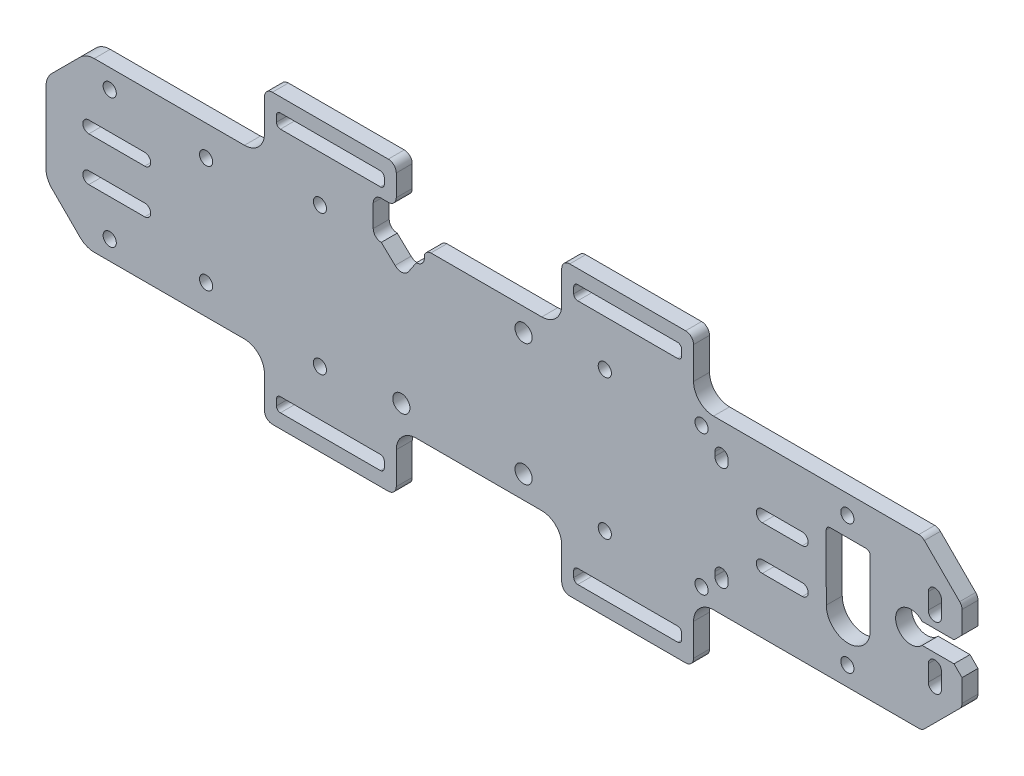
SolidWorks part; units mm, degrees
ref_plane "Спереди" through (0, 0, 0) normal (0, 0, 1) x (1, 0, 0)
ref_plane "Сверху" through (0, 0, 0) normal (0, 1, 0) x (1, 0, 0)
ref_plane "Справа" through (0, 0, 0) normal (1, 0, 0) x (0, 0, -1)
other "Configuration Table"
sketch "Эскиз1" plane through (0, 0, 0) normal (0, 0, 1) x (1, 0, 0)
  line L0 (-89.22, -7.8952) -> (91.7, -7.8952) construction
  line L1 (102, -28.8952) -> (-84.2169, -28.8952)
  line L2 (104, -26.8952) -> (104, -21.0952)
  line L3 (102, 13.1048) -> (-84.2169, 13.1048)
  line L7 (102, -19.0952) -> (93.7, -19.0952) construction
  line L8 (104, 13.1048) -> (88.64, 13.1048)
  line L9 (104, 11.1048) -> (104, 5.3048)
  line L10 (102, 3.3048) -> (93.7, 3.3048) construction
  line L13 (104, -28.8952) -> (88.64, -28.8952)
  line L14 (104, -28.8952) -> (104, -21.0952)
  line L15 (91.7, 1.3048) -> (91.7, -17.0952) construction
  line L16 (104, 5.3048) -> (104, 13.1048)
  line L17 (-87.6082, -28.8952) -> (-88, -28.8952)
  line L36 (-86, 4.8548) -> (-86, 12.1549) construction
  line L42 (-86, 4.8548) -> (-86, 23.4206) construction
  line L47 (-6.6, 7.4048) -> (24, 7.4048) construction
  line L48 (-6.6, 7.4048) -> (-6.6, -23.1952) construction
  line L49 (-6.6, -23.1952) -> (24, -23.1952) construction
  line L50 (24, 7.4048) -> (24, -23.1952) construction
  line L51 (-6.6, 7.4048) -> (24, -23.1952) construction
  line L52 (-6.6, -23.1952) -> (24, 7.4048) construction
  line L65 (-86, -20.6452) -> (-86, -30.5656) construction
  line L66 (-84.2169, -28.8952) -> (-84.6953, -28.8952)
  line L69 (97, 8.3048) -> (-87.65, 8.3048) construction
  line L70 (97, 8.3048) -> (97, -24.0952) construction
  line L71 (97, -24.0952) -> (-87.65, -24.0952) construction
  line L72 (-87.65, 8.3048) -> (-87.65, -24.0952) construction
  line L73 (-87.6082, 13.1048) -> (-84.2169, 13.1048)
  line L74 (-87.6082, -28.8952) -> (-84.2169, -28.8952)
  line L76 (-98, -14.8452) -> (-98, -18.8952)
  line L77 (-88, 13.1048) -> (-87.6082, 13.1048)
  line L78 (-98, -14.8452) -> (-98, 3.1048)
  line L79 (-88, -28.8952) -> (-98, -18.8952)
  line L80 (-98, 3.1048) -> (-88, 13.1048)
  line L82 (104, 5.3048) -> (104, -21.0952)
  circle A0 centre (97, 8.3048) radius 1.65 construction
  circle A1 centre (97, -24.0952) radius 1.65 construction
  arc A20 (102, -19.0952) -> (104, -21.0952) centre (102, -21.0952) cw construction
  arc A21 (104, 5.3048) -> (102, 3.3048) centre (102, 5.3048) cw construction
  arc A23 (93.7, -19.0952) -> (91.7, -17.0952) centre (93.7, -17.0952) cw construction
  arc A24 (93.7, 3.3048) -> (91.7, 1.3048) centre (93.7, 1.3048) ccw construction
  circle A25 centre (-87.65, 4.8548) radius 1.65 construction
  circle A30 centre (-87.65, -20.6452) radius 1.65 construction
  circle A33 centre (-6.6, 7.4048) radius 1.65 construction
  circle A34 centre (24, 7.4048) radius 1.65 construction
  circle A35 centre (24, -23.1952) radius 1.65 construction
  circle A36 centre (-6.6, -23.1952) radius 1.65 construction
  circle A43 centre (-87.65, -24.0952) radius 1.65
  circle A44 centre (-87.65, 8.3048) radius 1.65
  point P0 (0, 0)
  point P15 (-98, -28.8952)
  point P53 (-1.042, -7.8952)
  point P55 (91.7, -19.0952)
  point P58 (91.7, 3.3048)
  point P59 (-85.0378, -28.8952)
  point P60 (-98, 0)
  point P66 (-85.0378, 13.1048)
  point P70 (8.7, -7.8952)
  point P78 (-86, 13.1048)
  point P80 (-89.22, -28.8952)
  point P82 (-86, -28.8952)
  point P90 (-89.22, 13.1048)
  point P91 (-98, 13.1048)
  dimension "D4" = 16.2
  dimension "D5" = 7
  dimension "D13" = 16.2
  dimension "D14" = 2
  dimension "D15" = 2
  dimension "D17" = 2
  dimension "D19" = 2
  dimension "D8" = 3.3
  dimension "D20" = 191.65
  dimension "D21" = 8.25
  dimension "D22" = 30.6
  dimension "D23" = 12.3
  dimension "D26" = 80
  dimension "D27" = 3.3
  dimension "D29" = 3.3
  dimension "D3" = 9.8
  dimension "D18" = 42
  dimension "D24" = 30.6
extrude "Бобышка-Вытянуть1" add sketch "Эскиз1" along normal blind 4 contours L1 L2 A20 L7 A23 L15 A24 L10 A21 L9 L3 A1 A0 A25 A30 region at (4.3526, -7.8952, 0)
sketch "Эскиз2" plane through (0, 0, 4) normal (0, 0, 1) x (1, 0, 0)
  circle A0 centre (-87.65, -24.0952) radius 1.65 construction
  circle A1 centre (-87.65, 8.3048) radius 1.65 construction
  circle A3 centre (-87.65, -24.0952) radius 1.65 construction
  circle A6 centre (97, 8.3048) radius 1.65 construction
  circle A8 centre (97, -24.0952) radius 1.65 construction
  circle A10 centre (-6.6, 7.4048) radius 1.65 construction
  circle A12 centre (24, 7.4048) radius 1.65 construction
  circle A14 centre (24, -23.1952) radius 1.65 construction
  circle A16 centre (-6.6, -23.1952) radius 1.65 construction
  circle A17 centre (-87.65, 8.3048) radius 1.65 construction
  dimension "D1" = 30.6
  dimension "D2" = 30.6
  dimension "D5" = 30.6
  dimension "D6" = 30.6
sketch "Эскиз5" plane through (0, 0, 0) normal (0, 0, -1) x (-1, 0, 0)
  line L0 (88, -7.8952) -> (3.7318, -7.8952) construction
  line L1 (98, -18.8952) -> (98, 3.1048) construction
  line L2 (76, 9.3548) -> (91, 9.3548) construction
  line L3 (91, 9.3548) -> (76, 9.3548) construction
  line L4 (91, 9.3548) -> (91, -25.1452) construction
  line L5 (91, -25.1452) -> (76, -25.1452) construction
  line L6 (76, 9.3548) -> (76, -25.1452) construction
  line L7 (91, 9.3548) -> (76, -25.1452) construction
  line L8 (91, -25.1452) -> (76, 9.3548) construction
  line L9 (76, 11.1048) -> (91, 11.1048) construction
  line L10 (76, 7.6048) -> (91, 7.6048) construction
  line L11 (98, 1.0542) -> (62.57, 1.0542) construction
  line L12 (51.7224, 4.7048) -> (83.4687, 4.7048) construction
  line L14 (76, -3.8952) -> (91, -3.8952) construction
  line L15 (76, -0.3952) -> (91, -0.3952) construction
  line L16 (76, -2.1452) -> (91, -2.1452) construction
  line L17 (76, -15.3952) -> (91, -15.3952) construction
  line L18 (76, -11.8952) -> (91, -11.8952) construction
  line L19 (76, -13.6452) -> (91, -13.6452) construction
  line L20 (76, -26.8952) -> (91, -26.8952) construction
  line L21 (76, -23.3952) -> (91, -23.3952) construction
  line L22 (76, -25.1452) -> (91, -25.1452) construction
  line L23 (88, 13.1048) -> (88, -28.8952) construction
  arc A0 (76, 11.1048) -> (76, 7.6048) centre (76, 9.3548) ccw construction
  arc A1 (91, 7.6048) -> (91, 11.1048) centre (91, 9.3548) ccw construction
  arc A2 (76, -0.3952) -> (76, -3.8952) centre (76, -2.1452) ccw construction
  arc A3 (91, -3.8952) -> (91, -0.3952) centre (91, -2.1452) ccw construction
  arc A4 (76, -11.8952) -> (76, -15.3952) centre (76, -13.6452) ccw construction
  arc A5 (91, -15.3952) -> (91, -11.8952) centre (91, -13.6452) ccw construction
  arc A6 (76, -23.3952) -> (76, -26.8952) centre (76, -25.1452) ccw construction
  arc A7 (91, -26.8952) -> (91, -23.3952) centre (91, -25.1452) ccw construction
  point P4 (83.5, -7.8952)
  point P9 (83.5, 9.3548)
  point P21 (83.5, -2.1452)
  point P28 (83.5, -13.6452)
  point P35 (83.5, -25.1452)
  dimension "D1" = 7
  dimension "D2" = 15
  dimension "D3" = 3.5
  dimension "D4" = 4
  dimension "D5" = 35.43
  dimension "D6" = 4
  dimension "D7" = 8
sketch "Эскиз7" plane through (0, 0, 0) normal (0, 0, -1) x (-1, 0, 0)
  line L1 (-42, 28.1048) -> (-42, 13.1048) construction
  line L2 (98, -7.8952) -> (-91.7, -7.8952) construction
  line L3 (98, -18.8952) -> (98, 3.1048) construction
  line L4 (-104, 13.1048) -> (-104, -28.8952) construction
  line L5 (-104, 13.1048) -> (88, 13.1048) construction
  line L8 (-27.5, 28.1048) -> (-56.5, 28.1048) construction
  line L10 (-56.5, 28.1048) -> (-27.5, 28.1048)
  line L22 (17.92, 28.1048) -> (46.92, 28.1048) construction
  line L23 (-54.5, 24.6048) -> (-29.5, 24.6048)
  line L24 (-58.5, 26.1048) -> (-58.5, 18.1048)
  line L25 (-55.5, 23.6048) -> (-55.5, 22.1048)
  line L44 (-8.7, 7.4048) -> (-8.7, -18.2728) construction
  line L45 (-4.79, 7.4048) -> (-4.79, -18.2728) construction
  line L46 (-54.5, -36.8952) -> (-29.5, -36.8952)
  line L47 (-28.5, -39.3952) -> (-28.5, -37.8952)
  line L48 (-54.5, -40.3952) -> (-29.5, -40.3952)
  line L49 (-55.5, -39.3952) -> (-55.5, -37.8952)
  line L66 (-54.5, 21.1048) -> (-29.5, 21.1048)
  line L70 (-58.5, -41.8952) -> (-58.5, -33.8952)
  line L78 (-56.5, -43.8952) -> (-27.5, -43.8952)
  line L79 (-25.5, -41.8952) -> (-25.5, -33.8952)
  line L80 (-25.5, -28.8952) -> (-20.5, -28.8952)
  line L81 (-58.5, -28.8952) -> (-25.5, -28.8952)
  line L82 (-63.5, -28.8952) -> (-58.5, -28.8952)
  line L83 (32.42, 28.1048) -> (32.42, 13.1048) construction
  line L84 (15.92, 13.1048) -> (10.92, 13.1048)
  line L87 (53.92, 13.1048) -> (48.92, 13.1048)
  line L106 (-58.5, 13.1048) -> (-25.5, 13.1048)
  line L107 (-25.5, 26.1048) -> (-25.5, 18.1048)
  line L108 (-28.5, 23.6048) -> (-28.5, 22.1048)
  line L110 (18.92, 23.6048) -> (18.92, 22.1048)
  line L111 (-63.5, 13.1048) -> (-58.5, 13.1048)
  line L112 (-25.5, 13.1048) -> (-20.5, 13.1048)
  line L128 (15.92, 26.1048) -> (15.92, 18.1048)
  line L129 (48.92, 13.1048) -> (15.92, 13.1048)
  line L130 (53.92, -28.8952) -> (48.92, -28.8952)
  line L131 (48.92, -28.8952) -> (15.92, -28.8952)
  line L132 (15.92, -28.8952) -> (10.92, -28.8952)
  line L133 (15.92, -41.8952) -> (15.92, -33.8952)
  line L134 (46.92, -43.8952) -> (17.92, -43.8952)
  line L135 (48.92, -41.8952) -> (48.92, -33.8952)
  line L136 (44.92, 21.1048) -> (19.92, 21.1048)
  line L137 (45.92, -39.3952) -> (45.92, -37.8952)
  line L138 (44.92, -40.3952) -> (19.92, -40.3952)
  line L139 (18.92, -39.3952) -> (18.92, -37.8952)
  line L140 (44.92, -36.8952) -> (19.92, -36.8952)
  line L141 (45.92, 23.6048) -> (45.92, 22.1048)
  line L142 (48.92, 26.1048) -> (48.92, 18.1048)
  line L143 (44.92, 24.6048) -> (19.92, 24.6048)
  line L144 (46.92, 28.1048) -> (17.92, 28.1048)
  arc A70 (-29.5, 24.6048) -> (-28.5, 23.6048) centre (-29.5, 23.6048) cw
  arc A71 (-29.5, 21.1048) -> (-28.5, 22.1048) centre (-29.5, 22.1048) ccw
  arc A72 (-55.5, 22.1048) -> (-54.5, 21.1048) centre (-54.5, 22.1048) ccw
  arc A73 (-54.5, 24.6048) -> (-55.5, 23.6048) centre (-54.5, 23.6048) ccw
  arc A74 (-27.5, 28.1048) -> (-25.5, 26.1048) centre (-27.5, 26.1048) cw
  arc A75 (-56.5, 28.1048) -> (-58.5, 26.1048) centre (-56.5, 26.1048) ccw
  arc A76 (-20.5, 13.1048) -> (-25.5, 18.1048) centre (-20.5, 18.1048) cw
  arc A77 (-63.5, 13.1048) -> (-58.5, 18.1048) centre (-63.5, 18.1048) ccw
  arc A78 (-29.5, -36.8952) -> (-28.5, -37.8952) centre (-29.5, -37.8952) cw
  arc A79 (-29.5, -40.3952) -> (-28.5, -39.3952) centre (-29.5, -39.3952) ccw
  arc A80 (-55.5, -37.8952) -> (-54.5, -36.8952) centre (-54.5, -37.8952) cw
  arc A81 (-54.5, -40.3952) -> (-55.5, -39.3952) centre (-54.5, -39.3952) cw
  arc A82 (-63.5, -28.8952) -> (-58.5, -33.8952) centre (-63.5, -33.8952) cw
  arc A83 (-56.5, -43.8952) -> (-58.5, -41.8952) centre (-56.5, -41.8952) cw
  arc A84 (-27.5, -43.8952) -> (-25.5, -41.8952) centre (-27.5, -41.8952) ccw
  arc A85 (-20.5, -28.8952) -> (-25.5, -33.8952) centre (-20.5, -33.8952) ccw
  arc A102 (10.92, -28.8952) -> (15.92, -33.8952) centre (10.92, -33.8952) cw
  arc A103 (17.92, -43.8952) -> (15.92, -41.8952) centre (17.92, -41.8952) cw
  arc A104 (46.92, -43.8952) -> (48.92, -41.8952) centre (46.92, -41.8952) ccw
  arc A105 (53.92, -28.8952) -> (48.92, -33.8952) centre (53.92, -33.8952) ccw
  arc A106 (44.92, -40.3952) -> (45.92, -39.3952) centre (44.92, -39.3952) ccw
  arc A107 (45.92, -37.8952) -> (44.92, -36.8952) centre (44.92, -37.8952) ccw
  arc A108 (19.92, -40.3952) -> (18.92, -39.3952) centre (19.92, -39.3952) cw
  arc A109 (19.92, -36.8952) -> (18.92, -37.8952) centre (19.92, -37.8952) ccw
  arc A110 (53.92, 13.1048) -> (48.92, 18.1048) centre (53.92, 18.1048) cw
  arc A111 (10.92, 13.1048) -> (15.92, 18.1048) centre (10.92, 18.1048) ccw
  arc A112 (46.92, 28.1048) -> (48.92, 26.1048) centre (46.92, 26.1048) cw
  arc A113 (17.92, 28.1048) -> (15.92, 26.1048) centre (17.92, 26.1048) ccw
  arc A114 (44.92, 24.6048) -> (45.92, 23.6048) centre (44.92, 23.6048) cw
  arc A115 (45.92, 22.1048) -> (44.92, 21.1048) centre (44.92, 22.1048) cw
  arc A116 (19.92, 21.1048) -> (18.92, 22.1048) centre (19.92, 22.1048) cw
  arc A117 (19.92, 24.6048) -> (18.92, 23.6048) centre (19.92, 23.6048) ccw
  point P12 (-8.7, 13.1048)
  point P21 (-42, 23.8548)
  point P31 (-55.5, 21.1048)
  point P35 (-55.5, 24.6048)
  point P38 (-25.5, 28.1048)
  point P126 (15.92, 28.1048)
  point P127 (45.92, 24.6048)
  point P128 (45.92, 21.1048)
  point P129 (32.42, 23.8548)
  dimension "D5" = 45.5
  dimension "D6" = 3.5
  dimension "D7" = 3.5
  dimension "D8" = 1
  dimension "D9" = 2
  dimension "D10" = 5
  dimension "D1" = 27
  dimension "D2" = 3.91
  dimension "D4" = 13.5
extrude "Бобышка-Вытянуть3" add sketch "Эскиз7" against normal up to surface (4 mm away) up to face at (-86, 8.3048, 4)
sketch "Эскиз31" plane through (0, 0, 4) normal (0, 0, 1) x (1, 0, 0)
  line L0 (-14.65, 7.4048) -> (15.95, -23.1952) construction
  line L1 (15.95, 7.4048) -> (-14.65, -23.1952) construction
  line L3 (0.65, -7.8952) -> (0.65, 7.4048) construction
  line L5 (0.65, -7.8952) -> (-22.9584, -7.8952) construction
  circle A0 centre (-14.65, 7.4048) radius 2.15
  circle A1 centre (15.95, 7.4048) radius 2.15
  circle A2 centre (15.95, -23.1952) radius 2.15
  circle A3 centre (-14.65, -23.1952) radius 2.15
  circle A22 centre (97, 8.3048) radius 1.65
  circle A24 centre (97, -24.0952) radius 1.65
  circle A42 centre (36.2831, 9.6048) radius 1.65
  circle A48 centre (-35.0334, -25.3952) radius 1.65
  circle A50 centre (-35.0334, 9.6048) radius 1.65
  circle A52 centre (36.2831, -25.3952) radius 1.65
  dimension "D1" = 4.3
extrude "Вырез-Вытянуть13" cut sketch "Эскиз31" against normal through all
sketch "Эскиз9" plane through (0, 0, 0) normal (0, 0, -1) x (-1, 0, 0)
  line L1 (-17.149, -25.8952) -> (-17.149, -25.6051) construction
  line L11 (-24, -23.1952) -> (6.6, -23.1952) construction
  line L13 (-28.9705, -34.5374) -> (-26, -34.5374) construction
  line L14 (-26, -34.5374) -> (-29.3895, -34.5374) construction
  line L15 (-29.8895, -25.6015) -> (-29.8895, -34.0374) construction
  line L16 (-14.149, -28.8952) -> (-25.5, -35.0374) construction
  line L17 (-24, 7.4048) -> (6.6, 7.4048) construction
  line L18 (6.6, 7.4048) -> (6.6, -23.1952) construction
  line L19 (1.6004, 7.4048) -> (13.3395, 7.4048)
  line L30 (-8.7, -7.8952) -> (15.3395, -7.8952) construction
  line L31 (8.1, 26.1048) -> (8.1, 20.7471)
  line L32 (13.3395, 18.7471) -> (10.1, 18.7471) construction
  line L39 (10.1, 18.7471) -> (13.3395, 18.7471)
  line L60 (15.3395, 9.4048) -> (15.3395, 16.7471)
  line L63 (15.3395, 21.1048) -> (15.3395, -36.8952) construction
  line L67 (-4.79, 13.1048) -> (-4.79, -28.8952) construction
  line L68 (-20.5, 13.1048) -> (10.92, 13.1048) construction
  line L69 (10.92, -28.8952) -> (-20.5, -28.8952) construction
  line L70 (-29.449, -25.1051) -> (-17.649, -25.1051)
  line L71 (8.1, 20.7471) -> (-2.4126, 13.1048)
  line L72 (-20.5, 13.1048) -> (10.92, 13.1048) construction
  arc A0 (-17.149, -25.6051) -> (-17.649, -25.1051) centre (-17.649, -25.6051) ccw construction
  arc A3 (-14.149, -28.8952) -> (-17.149, -25.8952) centre (-14.149, -25.8952) cw construction
  arc A10 (-29.8895, -34.0374) -> (-29.3895, -34.5374) centre (-29.3895, -34.0374) ccw construction
  arc A11 (15.3395, 16.7471) -> (13.3395, 18.7471) centre (13.3395, 16.7471) ccw
  arc A18 (-25.5, -35.0374) -> (-26, -34.5374) centre (-26, -35.0374) ccw construction
  arc A19 (-0.3402, 8.9209) -> (1.6004, 7.4048) centre (1.6004, 9.4048) ccw
  arc A33 (-2.4126, 13.1048) -> (-0.3402, 8.9209) centre (-10.9328, 6.2793) cw
  arc A63 (15.3395, 9.4048) -> (13.3395, 7.4048) centre (13.3395, 9.4048) cw
  arc A65 (8.1, 20.7471) -> (10.1, 18.7471) centre (10.1, 20.7471) ccw
  arc A116 (-29.449, -25.1051) -> (-29.8895, -25.6015) centre (-29.3895, -25.6015) ccw construction
  dimension "D1" = 0.5
  dimension "D2" = 3
  dimension "D3" = 0.5
  dimension "D4" = 0.5
  dimension "D5" = 2
  dimension "D6" = 2
  dimension "D7" = 0
  dimension "0" = 0
extrude "Вырез-Вытянуть5" [suppressed] cut sketch "Эскиз9" against normal through all contours L71 A33 A19 L19 A63 L60 A11 L39 A65
sketch "Эскиз16" plane through (0, 0, 0) normal (0, 0, -1) x (-1, 0, 0)
  line L1 (-104, -7.8952) -> (98, -7.8952) construction
  line L2 (-104, 13.1048) -> (-104, -28.8952) construction
  line L3 (98, -18.8952) -> (98, 3.1048) construction
  line L28 (69.1216, -7.3748) -> (68.4911, 5.021)
  line L29 (53.2265, 7.5333) -> (48.9872, 5.0858)
  line L30 (48.9872, 5.0858) -> (48.9872, -0.6416)
  line L31 (49.9202, -1.5746) -> (52.2048, -1.5746)
  line L32 (53.4548, -2.8246) -> (53.4548, -12.8246)
  line L33 (52.2048, -14.0746) -> (49.9202, -14.0746)
  line L34 (48.9872, -15.0076) -> (48.9872, -20.5797)
  line L35 (48.9872, -20.5797) -> (53.2862, -23.169)
  line L36 (68.5124, -21.6919) -> (69.1259, -8.1422)
  line L37 (69.1259, -8.1422) -> (69.1422, -7.7807)
  line L38 (69.1422, -7.7807) -> (69.1216, -7.3748)
  line L39 (-66.8553, -25.6716) -> (-60.2225, -29.8755)
  line L40 (-59.4548, -29.4532) -> (-59.4548, -22.7157)
  line L41 (-59.8298, -22.3407) -> (-60.0798, -22.3407)
  line L42 (-60.7048, -21.7157) -> (-60.7048, -21.2157)
  line L43 (-60.0798, -20.5907) -> (-59.8298, -20.5907)
  line L44 (-59.4548, -20.2157) -> (-59.4548, 4.2843)
  line L45 (-59.8298, 4.6593) -> (-60.0798, 4.6593)
  line L46 (-60.7048, 5.2843) -> (-60.7048, 5.7843)
  line L47 (-60.0798, 6.4093) -> (-59.8298, 6.4093)
  line L48 (-59.4548, 6.7843) -> (-59.4548, 13.5155)
  line L49 (-60.2222, 13.938) -> (-66.8553, 9.7402)
  line L50 (-66.8553, 9.7402) -> (-66.8956, 9.5525)
  line L51 (-69.8496, 5.5343) -> (-69.8496, -5.3657)
  line L52 (-68.8496, -6.3657) -> (-63.0418, -6.3657)
  line L53 (-63.0418, -9.5657) -> (-68.8496, -9.5657)
  line L54 (-69.8496, -10.5657) -> (-69.8496, -21.4657)
  line L55 (-66.8956, -25.4839) -> (-66.8553, -25.6716)
  line L60 (-63.8325, -21.4657) -> (-63.8325, -20.4657)
  line L61 (-67.1325, -20.4657) -> (-67.1325, -21.4657)
  line L62 (-67.1325, 5.5343) -> (-67.1325, 4.5343)
  line L63 (-63.8325, 4.5343) -> (-63.8325, 5.5343)
  line L64 (-59.4548, -7.9657) -> (53.4548, -7.8246) construction
  line L65 (-61.4427, -7.9101) -> (69.1364, -7.9101) construction
  arc A46 (68.4911, 5.021) -> (68.5175, 5.5343) centre (63.5175, 5.5343) ccw
  arc A47 (68.5175, 5.5343) -> (66.9578, 9.1625) centre (63.5175, 5.5343) ccw
  arc A48 (66.9578, 9.1625) -> (62.0801, 10.267) centre (61.4143, -3.9965) ccw
  arc A49 (62.0801, 10.267) -> (61.5568, 9.7675) centre (62.0568, 9.7675) ccw
  arc A50 (61.5568, 9.7675) -> (61.6261, 9.5136) centre (62.0568, 9.7675) ccw
  arc A51 (61.8548, 8.6754) -> (61.6261, 9.5136) centre (60.2048, 8.6754) ccw
  arc A52 (58.5548, 8.6754) -> (61.8548, 8.6754) centre (60.2048, 8.6754) ccw
  arc A53 (58.6507, 9.2296) -> (58.5548, 8.6754) centre (60.2048, 8.6754) ccw
  arc A54 (58.6507, 9.2296) -> (58.6797, 9.3975) centre (58.1797, 9.3975) ccw
  arc A55 (58.6797, 9.3975) -> (58.0623, 9.8835) centre (58.1797, 9.3975) ccw
  arc A56 (58.0623, 9.8835) -> (54.3387, 8.4062) centre (61.4143, -3.9965) ccw
  arc A57 (53.2265, 7.5333) -> (54.3387, 8.4062) centre (50.7266, 11.8635) ccw
  arc A58 (48.9872, -0.6416) -> (49.1702, -0.8246) centre (49.4202, -0.3916) ccw
  arc A59 (49.1702, -0.8246) -> (49.9202, -1.5746) centre (49.9202, -0.8246) ccw
  arc A60 (53.4548, -2.8246) -> (52.2048, -1.5746) centre (52.2048, -2.8246) ccw
  arc A61 (52.2048, -14.0746) -> (53.4548, -12.8246) centre (52.2048, -12.8246) ccw
  arc A62 (49.9202, -14.0746) -> (49.1702, -14.8246) centre (49.9202, -14.8246) ccw
  arc A63 (49.1702, -14.8246) -> (48.9872, -15.0076) centre (49.4202, -15.2576) ccw
  arc A64 (54.3467, -24.0245) -> (53.2862, -23.169) centre (50.7065, -27.4521) ccw
  arc A65 (54.3467, -24.0245) -> (58.0449, -25.5036) centre (61.9789, -10.3045) ccw
  arc A66 (58.0449, -25.5036) -> (58.6434, -24.8579) centre (58.1702, -25.0196) ccw
  arc A67 (58.5548, -24.3246) -> (58.6434, -24.8579) centre (60.2048, -24.3246) ccw
  arc A68 (61.8548, -24.3246) -> (58.5548, -24.3246) centre (60.2048, -24.3246) ccw
  arc A69 (61.5842, -25.2301) -> (61.8548, -24.3246) centre (60.2048, -24.3246) ccw
  arc A70 (61.5842, -25.2301) -> (62.0029, -26.0044) centre (62.0022, -25.5044) ccw
  arc A71 (62.0029, -26.0044) -> (66.7842, -25.251) centre (61.9789, -10.3045) ccw
  arc A72 (66.7842, -25.251) -> (68.5124, -21.6919) centre (63.5175, -21.4657) ccw
  arc A73 (-60.2225, -29.8755) -> (-59.4548, -29.4532) centre (-59.9548, -29.4532) ccw
  arc A74 (-59.4548, -22.7157) -> (-59.8298, -22.3407) centre (-59.8298, -22.7157) ccw
  arc A75 (-60.7048, -21.7157) -> (-60.0798, -22.3407) centre (-60.0798, -21.7157) ccw
  arc A76 (-60.0798, -20.5907) -> (-60.7048, -21.2157) centre (-60.0798, -21.2157) ccw
  arc A77 (-59.8298, -20.5907) -> (-59.4548, -20.2157) centre (-59.8298, -20.2157) ccw
  arc A78 (-59.4548, 4.2843) -> (-59.8298, 4.6593) centre (-59.8298, 4.2843) ccw
  arc A79 (-60.7048, 5.2843) -> (-60.0798, 4.6593) centre (-60.0798, 5.2843) ccw
  arc A80 (-60.0798, 6.4093) -> (-60.7048, 5.7843) centre (-60.0798, 5.7843) ccw
  arc A81 (-59.8298, 6.4093) -> (-59.4548, 6.7843) centre (-59.8298, 6.7843) ccw
  arc A82 (-59.4548, 13.5155) -> (-60.2222, 13.938) centre (-59.9548, 13.5155) ccw
  arc A83 (-67.2398, 9.1788) -> (-66.8956, 9.5525) centre (-67.3845, 9.6574) ccw
  arc A84 (-67.2398, 9.1788) -> (-69.7742, 6.3425) centre (-66.184, 5.685) ccw
  arc A85 (-69.7742, 6.3425) -> (-69.8496, 5.5343) centre (-65.4825, 5.5343) ccw
  arc A86 (-69.8496, -5.3657) -> (-68.8496, -6.3657) centre (-68.8496, -5.3657) ccw
  arc A87 (-63.0418, -9.5657) -> (-63.0418, -6.3657) centre (-63.0418, -7.9657) ccw
  arc A88 (-68.8496, -9.5657) -> (-69.8496, -10.5657) centre (-68.8496, -10.5657) ccw
  arc A89 (-69.8496, -21.4657) -> (-69.7742, -22.2739) centre (-65.4825, -21.4657) ccw
  arc A90 (-69.7742, -22.2739) -> (-67.2398, -25.1102) centre (-66.184, -21.6164) ccw
  arc A91 (-66.8956, -25.4839) -> (-67.2398, -25.1102) centre (-67.3845, -25.5888) ccw
  arc A96 (65.1675, -21.4657) -> (61.8675, -21.4657) centre (63.5175, -21.4657) ccw
  arc A97 (61.8675, -21.4657) -> (65.1675, -21.4657) centre (63.5175, -21.4657) ccw
  arc A100 (65.1675, 5.5343) -> (61.8675, 5.5343) centre (63.5175, 5.5343) ccw
  arc A101 (61.8675, 5.5343) -> (65.1675, 5.5343) centre (63.5175, 5.5343) ccw
  arc A104 (-63.8325, -20.4657) -> (-67.1325, -20.4657) centre (-65.4825, -20.4657) ccw
  arc A105 (-67.1325, -21.4657) -> (-63.8325, -21.4657) centre (-65.4825, -21.4657) ccw
  arc A106 (-63.8325, 5.5343) -> (-67.1325, 5.5343) centre (-65.4825, 5.5343) ccw
  arc A107 (-67.1325, 4.5343) -> (-63.8325, 4.5343) centre (-65.4825, 4.5343) ccw
extrude "Вырез-Вытянуть6" cut sketch "Эскиз16" against normal up to surface (4 mm away) contours L62 A107 L63 A106 | L61 A105 L60 A104 | A100 A101 | A96 A97 | L62 A107 L63 A106 | L60 A104 L61 A105 region at (65.4825, -20.9657, 0) region at (65.4825, 5.0343, 0) region at (-63.5175, -21.4657, 0) region at (-63.5175, 5.5343, 0) up to face at (-33.3834, 9.6048, 4)
sketch "Эскиз21" [suppressed] plane through (0, 0, 4) normal (0, 0, 1) x (1, 0, 0)
  line L0 (-12.4895, 18.2471) -> (-11.9895, 18.7471) construction
  line L1 (-12.4895, 9.8112) -> (-12.4895, 18.2471) construction
  line L3 (0.3105, 18.2471) -> (0.3105, 9.6771)
  line L4 (-11.9895, 9.1771) -> (-0.1895, 9.1771)
  line L36 (-12.4895, 18.2471) -> (-12.4895, 9.6771)
  line L37 (-0.1895, 18.7471) -> (-11.9895, 18.7471)
  arc A0 (-11.9895, 18.7471) -> (-12.4895, 18.2471) centre (-11.9895, 18.2471) ccw construction
  arc A1 (-0.1895, 9.1771) -> (0.3105, 9.6771) centre (-0.1895, 9.6771) ccw
  arc A76 (-12.4895, 9.6771) -> (-11.9895, 9.1771) centre (-11.9895, 9.6771) ccw
  arc A77 (-11.9895, 18.7471) -> (-12.4895, 18.2471) centre (-11.9895, 18.2471) ccw
  arc A78 (0.3105, 18.2471) -> (-0.1895, 18.7471) centre (-0.1895, 18.2471) ccw
  dimension "D1" = 0.5
extrude "Вырез-Вытянуть7" [suppressed] cut sketch "Эскиз21" against normal up to surface (4 mm away) contours L3 A1 L4 A76 L36 A77 L37 A78
sketch "Эскиз24" plane through (0, 0, 4) normal (0, 0, 1) x (1, 0, 0)
  line L0 (15.95, 7.4048) -> (-25.3205, 7.4048) construction
  line L1 (-10.92, -28.8952) -> (20.5, -28.8952) construction
  circle A0 centre (-14.65, -23.1952) radius 1.65 construction
  circle A1 centre (-14.65, 7.4048) radius 1.65 construction
  circle A2 centre (15.95, 7.4048) radius 1.65 construction
  circle A4 centre (15.95, -23.1952) radius 1.65 construction
  circle A34 centre (-8.25, -7.8952) radius 1.65 construction
  circle A36 centre (9.65, -7.8952) radius 1.65 construction
  circle A66 centre (60.5, 9.6048) radius 1.65
  circle A76 centre (60.5, -25.3952) radius 1.65
  circle A90 centre (-35.0334, -20.3952) radius 1.65 construction
  circle A116 centre (-35.0334, 4.6048) radius 1.65 construction
  dimension "D1" = 3.3
  dimension "D2" = 30.6
  dimension "D3" = 30.6
  dimension "D4" = 30.6
  dimension "D5" = 17.9
  dimension "D6" = 3.3
  dimension "D7" = 21
extrude "Вырез-Вытянуть10" cut sketch "Эскиз24" against normal up to surface (4 mm away) up to face at (65.4825, -20.9657, 0)
sketch "Эскиз27" plane through (0, 0, 4) normal (0, 0, 1) x (1, 0, 0)
  line L0 (-98, -7.8952) -> (104, -7.8952) construction
  line L2 (91.65, -2.0252) -> (91.65, -18.3152)
  line L3 (97, 8.3048) -> (97, -24.0952) construction
  line L4 (104, 5.3048) -> (104, -21.0952) construction
  line L5 (92.45, -19.1152) -> (101.55, -19.1152)
  line L6 (91.95, -2.0252) -> (91.95, -18.3152) construction
  line L7 (102.05, -18.3152) -> (102.05, -2.0252) construction
  line L8 (92.45, -18.8152) -> (101.55, -18.8152) construction
  line L9 (102.35, -18.3152) -> (102.35, -2.0252)
  line L10 (91.7, 1.3048) -> (91.7, -17.0952) construction
  line L11 (97, 8.3048) -> (97, -24.0952) construction
  line L12 (-98, -18.8952) -> (-98, 3.1048) construction
  arc A0 (102.35, -2.0252) -> (91.65, -2.0252) centre (97, -2.0252) ccw
  arc A1 (91.65, -18.3152) -> (92.45, -19.1152) centre (92.45, -18.3152) ccw
  circle A2 centre (97, -24.0952) radius 1.6
  circle A3 centre (97, 8.3048) radius 1.6
  arc A5 (101.55, -19.1152) -> (102.35, -18.3152) centre (101.55, -18.3152) ccw
  arc A10 (91.95, -18.3152) -> (92.45, -18.8152) centre (92.45, -18.3152) ccw construction
  arc A11 (102.05, -2.0252) -> (91.95, -2.0252) centre (97, -2.0252) ccw construction
  arc A12 (101.55, -18.8152) -> (102.05, -18.3152) centre (101.55, -18.3152) ccw construction
  dimension "D1" = 0.3
sketch "Эскиз28" plane through (0, 0, 0) normal (0, 0, -1) x (-1, 0, 0)
  line L0 (-104, 13.1048) -> (-104, -28.8952) construction
  line L4 (-140.7, 3.1048) -> (-140.7, -18.8952)
  line L5 (88, -28.8952) -> (98, -18.8952) construction
  line L6 (88, 13.1048) -> (117.6, 13.1048) construction
  line L8 (88, -28.8952) -> (117.6, -28.8952) construction
  line L9 (127.6, 3.1048) -> (127.6, -18.8952) construction
  line L10 (98, 3.1048) -> (88, 13.1048) construction
  line L11 (98, -18.8952) -> (98, 3.1048) construction
  line L12 (88, -28.8952) -> (98, -18.8952)
  line L13 (98, 3.1048) -> (88, 13.1048)
  line L14 (98, -18.8952) -> (98, 3.1048)
  line L15 (127.6, 13.1048) -> (117.6, 13.1048) construction
  line L16 (98, -7.8952) -> (127.6, -7.8952) construction
  line L17 (98, 3.1048) -> (127.6, 3.1048) construction
  line L18 (98, -18.8952) -> (127.6, -18.8952) construction
  line L19 (117.6, 13.1048) -> (127.6, 3.1048) construction
  line L20 (117.6, -28.8952) -> (127.6, -18.8952) construction
  line L24 (-130.7, 13.1048) -> (-130.7, -28.8952) construction
  line L25 (-130.7, 13.1048) -> (-140.7, 3.1048)
  line L26 (-140.7, -18.8952) -> (-130.7, -28.8952)
  line L29 (-130.7, -28.8952) -> (-104, -28.8952)
  line L30 (-130.7, 13.1048) -> (-104, 13.1048)
  line L32 (103.6, 13.1048) -> (103.6, -28.8952) construction
  line L33 (103.6, 3.1048) -> (93.6, 13.1048)
  line L34 (103.6, -18.8952) -> (93.6, -28.8952)
  line L35 (103.6, 3.1048) -> (103.6, -18.8952)
  line L36 (88, 13.1048) -> (93.6, 13.1048)
  line L37 (88, -28.8952) -> (93.6, -28.8952)
  line L41 (-104, 13.1048) -> (-104, -28.8952)
  point P1 (-140.7, -28.8952)
  point P3 (-140.7, 13.1048)
  dimension "D1" = 36.7
  dimension "D2" = 29.6
  dimension "D3" = 10
  dimension "D4" = 10
  dimension "D6" = 24
  dimension "D9" = 10
extrude "Бобышка-Вытянуть4" add sketch "Эскиз28" against normal up to surface (4 mm away) up to face at (62.15, 9.6048, 4)
sketch "Эскиз29" plane through (0, 0, 0) normal (0, 0, -1) x (-1, 0, 0)
  line L1 (-140.7, 3.1048) -> (-140.7, -18.8952) construction
  line L7 (-56.5, -43.8952) -> (-27.5, -43.8952) construction
  line L10 (132.9536, -7.8952) -> (138.3072, -7.8952) construction
  line L12 (122.6, 8.1048) -> (128.2272, 7.311)
  line L14 (140.5213, 4.6848) -> (136.0546, -2.7403)
  line L27 (122.6, -23.8952) -> (127.6, -18.8952)
  line L28 (127.6, -18.8952) -> (127.6, 3.1048)
  line L29 (127.6, 3.1048) -> (122.6, 8.1048)
  line L33 (140.5213, -20.4751) -> (136.0546, -13.05)
  line L34 (122.6, -23.8952) -> (128.2272, -23.1014)
  arc A35 (128.2272, 7.311) -> (135.664, 9.2432) centre (129.624, 17.213) ccw
  arc A36 (140.5213, 4.6848) -> (135.664, 9.2432) centre (137.7046, 6.5505) ccw
  arc A37 (140.5213, -20.4751) -> (135.664, -25.0335) centre (137.7046, -22.3408) cw
  arc A38 (128.2272, -23.1014) -> (135.664, -25.0335) centre (129.624, -33.0033) cw
  arc A39 (136.0546, -2.7403) -> (136.0546, -13.05) centre (144.6236, -7.8952) ccw
  dimension "D1" = 10
  dimension "D2" = 10
extrude "Бобышка-Вытянуть5" [suppressed] add sketch "Эскиз29" against normal up to surface (4 mm away)
sketch "xt90" plane through (0, 0, 0) normal (0, 0, 1) x (1, 0, 0)
  line L0 (173.0556, -0.0452) -> (173.0556, -15.7452) construction
  line L1 (102.711, 2.1054) -> (102.711, -14.2451)
  line L2 (-103.6, -7.8952) -> (300.0767, -7.8952) construction
  line L3 (-103.6, -18.8952) -> (-103.6, 3.1048) construction
  line L4 (97, 8.3048) -> (97, -24.0952) construction
  line L5 (173.0556, 4.6048) -> (173.0556, -20.3952) construction
  line L6 (91.9501, 2.5242) -> (91.968, -13.7768) construction
  line L7 (101.3617, 3.2578) -> (92.6909, 3.2694) construction
  line L8 (102.461, -14.2129) -> (102.461, 2.1571) construction
  line L20 (169.0056, -0.2452) -> (169.0056, -12.7452) construction
  line L21 (172.0056, -15.7452) -> (174.1056, -15.7452) construction
  line L22 (177.1056, -12.7452) -> (177.1056, -0.2452) construction
  line L23 (176.9056, -0.0452) -> (169.2056, -0.0452) construction
  line L24 (97, 3.5136) -> (97, -19.2824) construction
  line L25 (91.1619, -18.3152) -> (91.1619, -2.0252) construction
  line L26 (81.0619, -2.0252) -> (81.0619, -18.3152) construction
  line L27 (81.5619, -18.8152) -> (90.6619, -18.8152) construction
  line L28 (81.9878, -28.8952) -> (93.0878, -28.8952) construction
  line L29 (95.0878, -26.8952) -> (95.0878, 11.1048) construction
  line L30 (93.0878, 13.1048) -> (81.9878, 13.1048) construction
  line L31 (79.9878, 11.1048) -> (79.9878, -26.8952) construction
  line L39 (182.2056, -16.7404) -> (182.2056, 0.9501) construction
  line L40 (182.1353, 1.3184) -> (180.6759, 5.0024) construction
  line L41 (180.6056, 5.3707) -> (180.6056, 7.6798) construction
  line L42 (179.1056, 9.1798) -> (170.3056, 9.1798) construction
  line L43 (168.8056, 7.6798) -> (168.8056, 5.5239) construction
  line L44 (168.5939, 4.9086) -> (166.6173, 2.3761) construction
  line L45 (166.4056, 1.7608) -> (166.4056, -17.5511) construction
  line L46 (166.6173, -18.1664) -> (168.5939, -20.6989) construction
  line L47 (168.8056, -21.3142) -> (168.8056, -23.4702) construction
  line L48 (170.3056, -24.9702) -> (179.1056, -24.9702) construction
  line L49 (180.6056, -23.4702) -> (180.6056, -21.161) construction
  line L50 (180.6759, -20.7927) -> (182.1353, -17.1088) construction
  line L55 (102.711, -14.2231) -> (102.711, 2.1054)
  line L56 (101.3104, 3.5079) -> (92.6896, 3.5194)
  line L57 (91.7001, 2.5248) -> (91.718, -13.7768)
  line L58 (91.6733, 3.3031) -> (102.7733, 3.3031) construction
  line L59 (91.6733, 3.3031) -> (91.6733, -19.2869) construction
  line L60 (91.6733, -19.2869) -> (102.7733, -19.2869) construction
  line L61 (102.7733, 3.3031) -> (102.7733, -19.2869) construction
  line L62 (101.3104, 3.5079) -> (101.711, 3.5073)
  line L63 (102.711, 2.1054) -> (102.711, 2.5073)
  arc A0 (102.711, 2.5073) -> (101.711, 3.5073) centre (101.711, 2.5073) ccw
  circle A2 centre (97, -24.0952) radius 1.6
  circle A4 centre (97, 8.3048) radius 1.6
  arc A5 (101.1053, 3.3031) -> (101.0505, 3.2582) centre (101.711, 2.5073) ccw
  arc A10 (91.968, -13.7768) -> (102.461, -14.2129) centre (97.2233, -13.7816) ccw construction
  arc A11 (92.6909, 3.2694) -> (91.9501, 2.5242) centre (92.7001, 2.5195) ccw construction
  arc A12 (102.461, 2.1571) -> (101.3617, 3.2578) centre (101.711, 2.5073) ccw construction
  arc A17 (182.2056, 0.9501) -> (182.1353, 1.3184) centre (181.2056, 0.9501) ccw construction
  arc A20 (180.6056, 5.3707) -> (180.6759, 5.0024) centre (181.6056, 5.3707) ccw construction
  arc A21 (180.6056, 7.6798) -> (179.1056, 9.1798) centre (179.1056, 7.6798) ccw construction
  circle A24 centre (173.0556, 2.4048) radius 1.65 construction
  circle A25 centre (173.0556, -18.1952) radius 1.65 construction
  arc A26 (169.0056, -12.7452) -> (172.0056, -15.7452) centre (172.0056, -12.7452) ccw construction
  arc A27 (174.1056, -15.7452) -> (177.1056, -12.7452) centre (174.1056, -12.7452) ccw construction
  arc A28 (177.1056, -0.2452) -> (176.9056, -0.0452) centre (176.9056, -0.2452) ccw construction
  arc A29 (90.6619, -18.8152) -> (91.1619, -18.3152) centre (90.6619, -18.3152) ccw construction
  arc A30 (91.1619, -2.0252) -> (81.0619, -2.0252) centre (86.1119, -2.0252) ccw construction
  arc A31 (81.0619, -18.3152) -> (81.5619, -18.8152) centre (81.5619, -18.3152) ccw construction
  arc A32 (79.9878, -26.8952) -> (81.9878, -28.8952) centre (81.9878, -26.8952) ccw construction
  arc A33 (93.0878, -28.8952) -> (95.0878, -26.8952) centre (93.0878, -26.8952) ccw construction
  arc A34 (95.0878, 11.1048) -> (93.0878, 13.1048) centre (93.0878, 11.1048) ccw construction
  arc A35 (81.9878, 13.1048) -> (79.9878, 11.1048) centre (81.9878, 11.1048) ccw construction
  arc A36 (170.3056, 9.1798) -> (168.8056, 7.6798) centre (170.3056, 7.6798) ccw construction
  arc A37 (168.5939, 4.9086) -> (168.8056, 5.5239) centre (167.8056, 5.5239) ccw
  arc A38 (166.6173, 2.3761) -> (166.4056, 1.7608) centre (167.4056, 1.7608) ccw construction
  arc A39 (166.4056, -17.5511) -> (166.6173, -18.1664) centre (167.4056, -17.5511) ccw construction
  arc A40 (168.8056, -21.3142) -> (168.5939, -20.6989) centre (167.8056, -21.3142) ccw construction
  arc A41 (168.8056, -23.4702) -> (170.3056, -24.9702) centre (170.3056, -23.4702) ccw construction
  arc A42 (179.1056, -24.9702) -> (180.6056, -23.4702) centre (179.1056, -23.4702) ccw construction
  arc A43 (180.6759, -20.7927) -> (180.6056, -21.161) centre (181.6056, -21.161) ccw construction
  arc A44 (182.1353, -17.1088) -> (182.2056, -16.7404) centre (181.2056, -16.7404) ccw construction
  arc A49 (91.718, -13.7768) -> (102.711, -14.2231) centre (97.2233, -13.7816) ccw
  arc A51 (92.6896, 3.5194) -> (91.7001, 2.5248) centre (92.7001, 2.5195) ccw
  arc A52 (169.2056, -0.0452) -> (169.0056, -0.2452) centre (169.2056, -0.2452) ccw construction
  arc A53 (102.711, 2.1054) -> (101.3104, 3.5079) centre (101.711, 2.5073) ccw construction
  dimension "D3" = 3.3
  dimension "D4" = 1
  dimension "D2" = 3.3
  dimension "D5" = 2
  dimension "D1" = 0.25
extrude "Вырез-Вытянуть12" cut sketch "xt90" along normal through all contours A4 | L63 A0 L62 L56 A51 L57 A49 L55 | A2 | L20 A26 L21 A27 L22 A28 L23 A52 | A24 | A25 region at (97, 8.3048, 0)
fillet "Скругление1" radius 5 4 edges at (-93.6, 13.1048, 2) (-103.6, 3.1048, 2) (-103.6, -18.8952, 2) (-93.6, -28.8952, 2)
sketch "Эскиз32" plane through (0, 0, 0) normal (0, 0, -1) x (-1, 0, 0)
  line L0 (-15.95, 7.4048) -> (14.65, 7.4048) construction
  line L1 (-0.65, 7.4048) -> (-0.65, -23.1952) construction
  line L2 (-15.95, -23.1952) -> (14.65, -23.1952) construction
sketch "Эскиз34" plane through (0, 0, 0) normal (0, 0, -1) x (-1, 0, 0)
  line L3 (8.8864, 11.9369) -> (8.8864, 11.1476)
  line L5 (6.8869, 13.1048) -> (15.9202, 20.7436)
  line L6 (10.899, 9.1476) -> (12.8626, 6.21)
  line L7 (19.6867, 9.1736) -> (16.2094, 5.9248)
  line L98 (21.6867, 11.1736) -> (21.6867, 16.7436)
  line L99 (19.6867, 18.7436) -> (17.9202, 18.7436)
  arc A0 (17.9202, 18.7436) -> (15.9202, 20.7436) centre (17.9202, 20.7436) cw
  arc A1 (8.8864, 11.9369) -> (6.8869, 13.1048) centre (7.0641, 11.1127) ccw
  arc A2 (12.8626, 6.21) -> (16.2094, 5.9248) centre (14.65, 7.4048) ccw
  arc A3 (21.6867, 16.7436) -> (19.6867, 18.7436) centre (19.6867, 16.7436) ccw
  arc A6 (19.6867, 9.1736) -> (21.6867, 11.1736) centre (19.6867, 11.1736) ccw
  arc A7 (10.899, 9.1476) -> (8.8864, 11.1476) centre (10.8864, 11.1476) cw
  arc A138 (9.3867, 18.7436) -> (8.8867, 18.2436) centre (9.3867, 18.2436) ccw
  dimension "D1" = 2
  dimension "D2" = 2
extrude "Вырез-Вытянуть14" cut sketch "Эскиз34" against normal through all contours A1 L5 A0 L99 A3 L98 A6 L7 A2 L6 A7 L3
sketch "Эскиз30" plane through (0, 0, 0) normal (0, 0, -1) x (-1, 0, 0)
  line L0 (-120.7, -7.8952) -> (-72.751, -7.8952) construction
  line L1 (-140.7, -7.8952) -> (-118.9, -7.8952) construction
  line L2 (-140.7, 3.1048) -> (-140.7, -18.8952) construction
  line L3 (-140.7, -7.8952) -> (-95.7, -7.8952) construction
  line L6 (-118.9, -2.0952) -> (-118.9, -5.2952) construction
  line L8 (-120.7, -10.4952) -> (-118.9, -10.4952)
  line L11 (-118.9, -7.8952) -> (-118.9, -13.6952) construction
  line L24 (-130.7, -28.8952) -> (-63.5, -28.8952) construction
  line L25 (-140.7, 3.1048) -> (-103.25, 3.1048) construction
  line L26 (-140.7, -18.8952) -> (-103.25, -18.8952) construction
  line L27 (-125.1142, -19.4809) -> (-116.2858, -28.3094)
  line L29 (-125.7, -15.4952) -> (-125.7, -18.0667)
  line L30 (-140.7, -18.8952) -> (-130.7, -28.8952) construction
  line L31 (-130.7, 13.1048) -> (-140.7, 3.1048) construction
  line L32 (-130.7, 13.1048) -> (-63.5, 13.1048) construction
  line L33 (-130.7, -28.8952) -> (-114.8716, -28.8952)
  line L34 (-140.7, -18.8952) -> (-130.7, -28.8952)
  line L35 (-140.7, 3.1048) -> (-140.7, -18.8952)
  line L36 (-130.7, 13.1048) -> (-140.7, 3.1048)
  line L37 (-130.7, 13.1048) -> (-114.8716, 13.1048)
  line L39 (-140.7, 3.1048) -> (-103.25, 3.1048) construction
  line L40 (-130.7, 13.1048) -> (-114.8716, 13.1048)
  line L41 (-140.7, 3.1048) -> (-130.7, 13.1048)
  line L42 (-130.7, 13.1048) -> (-114.8716, 13.1048)
  line L43 (-125.7, -0.2952) -> (-125.7, 2.2764)
  line L44 (-125.1142, 3.6906) -> (-116.2858, 12.5191)
  line L45 (-120.7, -5.2952) -> (-118.9, -5.2952)
  line L46 (-118.9, -5.2952) -> (-115.7091, -5.2952)
  line L47 (-118.9, -10.4952) -> (-115.7091, -10.4952)
  line L48 (-118.9, -2.0952) -> (-118.9, 1.9048) construction
  line L49 (-120.55, 1.9048) -> (-120.55, -2.0952)
  line L50 (-117.25, -2.0952) -> (-117.25, 1.9048)
  line L51 (-120.55, -17.6952) -> (-120.55, -13.6952)
  line L52 (-117.25, -13.6952) -> (-117.25, -17.6952)
  line L53 (-125.7, -0.2952) -> (-125.7, -3.2952)
  line L54 (-123.7, -5.2952) -> (-120.7, -5.2952)
  line L55 (-125.7, -15.4952) -> (-125.7, -12.4952)
  line L56 (-123.7, -10.4952) -> (-120.7, -10.4952)
  line L57 (-125.7, -12.4952) -> (-123.7, -10.4952)
  line L58 (-125.7, -3.2952) -> (-123.7, -5.2952)
  arc A2 (-120.55, -2.0952) -> (-117.25, -2.0952) centre (-118.9, -2.0952) ccw
  arc A10 (-125.1142, -19.4809) -> (-125.7, -18.0667) centre (-123.7, -18.0667) cw
  arc A11 (-114.8716, -28.8952) -> (-116.2858, -28.3094) centre (-114.8716, -26.8952) cw
  arc A12 (-114.8716, 13.1048) -> (-116.2858, 12.5191) centre (-114.8716, 11.1048) ccw
  arc A13 (-125.1142, 3.6906) -> (-125.7, 2.2764) centre (-123.7, 2.2764) ccw
  arc A16 (-115.7091, -10.4952) -> (-115.7091, -5.2952) centre (-112.9, -7.8952) ccw
  arc A17 (-117.25, 1.9048) -> (-120.55, 1.9048) centre (-118.9, 1.9048) ccw
  arc A18 (-120.55, -13.6952) -> (-117.25, -13.6952) centre (-118.9, -13.6952) cw
  arc A19 (-117.25, -17.6952) -> (-120.55, -17.6952) centre (-118.9, -17.6952) cw
  point P4 (-118.9, -7.8952)
  point P16 (-114.45, -7.8952)
  point P47 (-125.7, -18.8952)
  point P58 (-125.7, 3.1048)
  point P59 (-125.7, -5.2952)
  point P60 (-125.7, -10.4952)
  dimension "D5" = 6
  dimension "D8" = 2
  dimension "D3" = 3.8277
extrude "Вырез-Вытянуть11" cut sketch "Эскиз30" against normal through all contours L27 A10 L29 L8 L37 L36 L35 L34 L33 | A2 L50 A17 L49 | A18 L52 A19 L51 region at (129.0028, -7.8952, 0)
sketch "Эскиз35" plane through (0, 0, 0) normal (0, 0, -1) x (-1, 0, 0)
  line L0 (103.6, -7.8952) -> (-188.7271, -7.8952) construction
  line L1 (-85.7, 4.4048) -> (-75.7, 4.4048) construction
  line L2 (-125.7, -3.2952) -> (-125.7, 2.2764) construction
  line L3 (-85.7, 4.4048) -> (-75.7, 4.4048) construction
  line L4 (-85.7, 5.9048) -> (-75.7, 5.9048) construction
  line L5 (-85.7, 2.9048) -> (-75.7, 2.9048) construction
  line L6 (103.6, -16.8241) -> (103.6, 1.0338) construction
  line L9 (-85.7, -20.1952) -> (-75.7, -20.1952) construction
  line L10 (-85.7, -21.6952) -> (-75.7, -21.6952) construction
  line L11 (-85.7, -18.6952) -> (-75.7, -18.6952) construction
  line L12 (-85.7, -3.8952) -> (-75.7, -3.8952)
  line L13 (-85.7, -0.8952) -> (-75.7, -0.8952)
  line L14 (-85.7, -2.3952) -> (-75.7, -2.3952) construction
  line L15 (-85.7, -14.8952) -> (-75.7, -14.8952)
  line L16 (-85.7, -11.8952) -> (-75.7, -11.8952)
  line L17 (-85.7, -13.3952) -> (-75.7, -13.3952) construction
  arc A0 (-85.7, 5.9048) -> (-85.7, 2.9048) centre (-85.7, 4.4048) ccw construction
  arc A1 (-75.7, 2.9048) -> (-75.7, 5.9048) centre (-75.7, 4.4048) ccw construction
  circle A4 centre (-118.9, -2.0952) radius 1.65 construction
  arc A5 (-85.7, -21.6952) -> (-85.7, -18.6952) centre (-85.7, -20.1952) cw construction
  arc A6 (-75.7, -18.6952) -> (-75.7, -21.6952) centre (-75.7, -20.1952) cw construction
  arc A7 (-85.7, -0.8952) -> (-85.7, -3.8952) centre (-85.7, -2.3952) ccw
  arc A8 (-75.7, -3.8952) -> (-75.7, -0.8952) centre (-75.7, -2.3952) ccw
  arc A9 (-85.7, -11.8952) -> (-85.7, -14.8952) centre (-85.7, -13.3952) ccw
  arc A10 (-75.7, -14.8952) -> (-75.7, -11.8952) centre (-75.7, -13.3952) ccw
  point P7 (-80.7, 4.4048)
  point P16 (-80.7, -20.1952)
  point P26 (-80.7, -2.3952)
  point P33 (-80.7, -13.3952)
  dimension "D3" = 1.5
  dimension "D6" = 1.5
  dimension "D7" = 1.5
  dimension "D1" = 40
  dimension "D2" = 10
  dimension "D4" = 5
  dimension "D5" = 4
  dimension "D8" = 4
extrude "Вырез-Вытянуть15" cut sketch "Эскиз35" against normal through all
sketch "Эскиз36" plane through (0, 0, 0) normal (0, 0, -1) x (-1, 0, 0)
  line L0 (103.6, -7.8952) -> (68.17, -7.8952) construction
  line L1 (103.6, -16.8241) -> (103.6, 1.0338) construction
  line L3 (85.885, -7.8952) -> (85.885, -15.3858) construction
  line L4 (78.885, -2.3952) -> (92.885, -2.3952) construction
  line L5 (78.885, -0.8952) -> (92.885, -0.8952)
  line L6 (78.885, -3.8952) -> (92.885, -3.8952)
  line L7 (78.885, -13.3952) -> (92.885, -13.3952) construction
  line L8 (78.885, -14.8952) -> (92.885, -14.8952)
  line L9 (78.885, -11.8952) -> (92.885, -11.8952)
  arc A0 (78.885, -0.8952) -> (78.885, -3.8952) centre (78.885, -2.3952) ccw
  arc A1 (92.885, -3.8952) -> (92.885, -0.8952) centre (92.885, -2.3952) ccw
  arc A2 (78.885, -14.8952) -> (78.885, -11.8952) centre (78.885, -13.3952) cw
  arc A3 (92.885, -11.8952) -> (92.885, -14.8952) centre (92.885, -13.3952) cw
  point P4 (85.885, -2.3952)
  point P10 (85.885, 0)
  point P17 (85.885, -13.3952)
  dimension "D3" = 1.5
  dimension "D1" = 35.43
  dimension "D2" = 7
  dimension "D4" = 4
extrude "Вырез-Вытянуть16" cut sketch "Эскиз36" against normal through all
sketch "Эскиз39" plane through (0, 0, 0) normal (0, 0, -1) x (-1, 0, 0)
  line L0 (-125.1142, 3.6906) -> (-128.6858, 0.1191)
  line L2 (-125.7, -3.2952) -> (-127.2716, -3.2952)
  line L4 (-125.1142, 3.6906) -> (-116.2858, 12.5191) construction
  line L5 (-99.85, -7.8952) -> (-134.3397, -7.8952) construction
  line L6 (-125.7, -3.2952) -> (-125.7, 2.2764) construction
  line L7 (-125.7, -3.2952) -> (-125.7, 2.2764)
  line L8 (-125.7, -12.4952) -> (-125.7, -18.0667)
  line L9 (-125.7, -12.4952) -> (-127.2716, -12.4952)
  line L10 (-125.1142, -19.4809) -> (-128.6858, -15.9094)
  arc A0 (-127.2716, -3.2952) -> (-128.6858, 0.1191) centre (-127.2716, -1.2952) cw
  arc A3 (-125.1142, 3.6906) -> (-125.7, 2.2764) centre (-123.7, 2.2764) ccw construction
  arc A5 (-125.1142, 3.6906) -> (-125.7, 2.2764) centre (-123.7, 2.2764) ccw
  arc A6 (-125.1142, -19.4809) -> (-125.7, -18.0667) centre (-123.7, -18.0667) cw
  arc A8 (-127.2716, -12.4952) -> (-128.6858, -15.9094) centre (-127.2716, -14.4952) ccw
  dimension "D1" = 2
extrude "Бобышка-Вытянуть7" [suppressed] add sketch "Эскиз39" against normal up to surface (4 mm away)
sketch "Эскиз40" [suppressed] plane through (0, 0, 0) normal (0, 0, -1) x (-1, 0, 0)
  line L0 (-119.928, 3.8768) -> (-119.928, -19.6671) construction
  line L1 (-125.6858, -1.8809) -> (-111.2858, 12.5191) construction
  line L2 (-125.6858, -13.9094) -> (-111.2858, -28.3094) construction
  line L4 (-99.85, -7.8952) -> (-139.6416, -7.8952) construction
  line L13 (-117.9058, 1.017) -> (-117.9058, 5.899)
  line L14 (-117.9058, 5.899) -> (-123.3669, 0.438)
  line L15 (-117.9058, -16.8073) -> (-117.9058, -21.6893)
  line L16 (-117.9058, -21.6893) -> (-123.3669, -16.2283)
  arc A0 (-121.7304, 0.1) -> (-117.9058, 1.017) centre (-119.928, 1.017) ccw
  arc A7 (-121.7304, 0.1) -> (-123.3669, 0.438) centre (-122.6598, -0.2691) ccw
  arc A8 (-121.7304, -15.8903) -> (-117.9058, -16.8073) centre (-119.928, -16.8073) cw
  arc A9 (-121.7304, -15.8903) -> (-123.3669, -16.2283) centre (-122.6598, -15.5212) cw
  dimension "D1" = 2
extrude "Вырез-Вытянуть19" [suppressed] cut sketch "Эскиз40" against normal through all
fillet "Скругление2" [suppressed] radius 5
sketch "Эскиз41" plane through (0, 0, 0) normal (0, 0, -1) x (-1, 0, 0)
  line L4 (-125.1142, 3.6906) -> (-116.2858, 12.5191) construction
  line L5 (-125.7, 2.2764) -> (-125.7, -3.2952) construction
  line L6 (-125.7, -3.2952) -> (-123.7, -5.2952) construction
  line L7 (-117.25, -2.0952) -> (-117.25, 1.9048) construction
  line L8 (-120.55, 1.9048) -> (-120.55, -2.0952) construction
  line L9 (-120.55, -17.6952) -> (-120.55, -13.6952) construction
  line L10 (-117.25, -13.6952) -> (-117.25, -17.6952) construction
  line L11 (-125.1142, -19.4809) -> (-116.2858, -28.3094) construction
  line L12 (-125.7, -12.4952) -> (-125.7, -18.0667) construction
  line L13 (-125.7, -12.4952) -> (-123.7, -10.4952) construction
  line L14 (-123.7, -10.4952) -> (-115.7091, -10.4952) construction
  line L15 (-123.7, -5.2952) -> (-115.7091, -5.2952) construction
  line L16 (-125.1142, 3.6906) -> (-116.2858, 12.5191)
  line L17 (-125.7, 2.2764) -> (-125.7, -3.2952)
  line L18 (-125.7, -3.2952) -> (-123.7, -5.2952)
  line L19 (-117.25, -2.0952) -> (-117.25, 1.9048)
  line L20 (-120.55, 1.9048) -> (-120.55, -2.0952)
  line L21 (-120.55, -17.6952) -> (-120.55, -13.6952)
  line L22 (-117.25, -13.6952) -> (-117.25, -17.6952)
  line L23 (-125.1142, -19.4809) -> (-116.2858, -28.3094)
  line L24 (-125.7, -12.4952) -> (-125.7, -18.0667)
  line L25 (-125.7, -12.4952) -> (-123.7, -10.4952)
  line L26 (-123.7, -10.4952) -> (-115.7091, -10.4952)
  line L27 (-123.7, -5.2952) -> (-115.7091, -5.2952)
  arc A4 (-114.8716, 13.1048) -> (-116.2858, 12.5191) centre (-114.8716, 11.1048) ccw construction
  arc A5 (-125.1142, 3.6906) -> (-125.7, 2.2764) centre (-123.7, 2.2764) ccw construction
  arc A6 (-117.25, 1.9048) -> (-120.55, 1.9048) centre (-118.9, 1.9048) ccw construction
  arc A7 (-120.55, -2.0952) -> (-117.25, -2.0952) centre (-118.9, -2.0952) ccw construction
  arc A8 (-117.25, -13.6952) -> (-120.55, -13.6952) centre (-118.9, -13.6952) ccw construction
  arc A9 (-120.55, -17.6952) -> (-117.25, -17.6952) centre (-118.9, -17.6952) ccw construction
  arc A10 (-116.2858, -28.3094) -> (-114.8716, -28.8952) centre (-114.8716, -26.8952) ccw construction
  arc A11 (-125.7, -18.0667) -> (-125.1142, -19.4809) centre (-123.7, -18.0667) ccw construction
  arc A12 (-115.7091, -10.4952) -> (-115.7091, -5.2952) centre (-112.9, -7.8952) ccw construction
  arc A13 (-114.8716, 13.1048) -> (-116.2858, 12.5191) centre (-114.8716, 11.1048) ccw
  arc A14 (-125.1142, 3.6906) -> (-125.7, 2.2764) centre (-123.7, 2.2764) ccw
  arc A15 (-117.25, 1.9048) -> (-120.55, 1.9048) centre (-118.9, 1.9048) ccw
  arc A16 (-120.55, -2.0952) -> (-117.25, -2.0952) centre (-118.9, -2.0952) ccw
  arc A17 (-117.25, -13.6952) -> (-120.55, -13.6952) centre (-118.9, -13.6952) ccw
  arc A18 (-120.55, -17.6952) -> (-117.25, -17.6952) centre (-118.9, -17.6952) ccw
  arc A19 (-116.2858, -28.3094) -> (-114.8716, -28.8952) centre (-114.8716, -26.8952) ccw
  arc A20 (-125.7, -18.0667) -> (-125.1142, -19.4809) centre (-123.7, -18.0667) ccw
  arc A21 (-115.7091, -10.4952) -> (-115.7091, -5.2952) centre (-112.9, -7.8952) ccw
